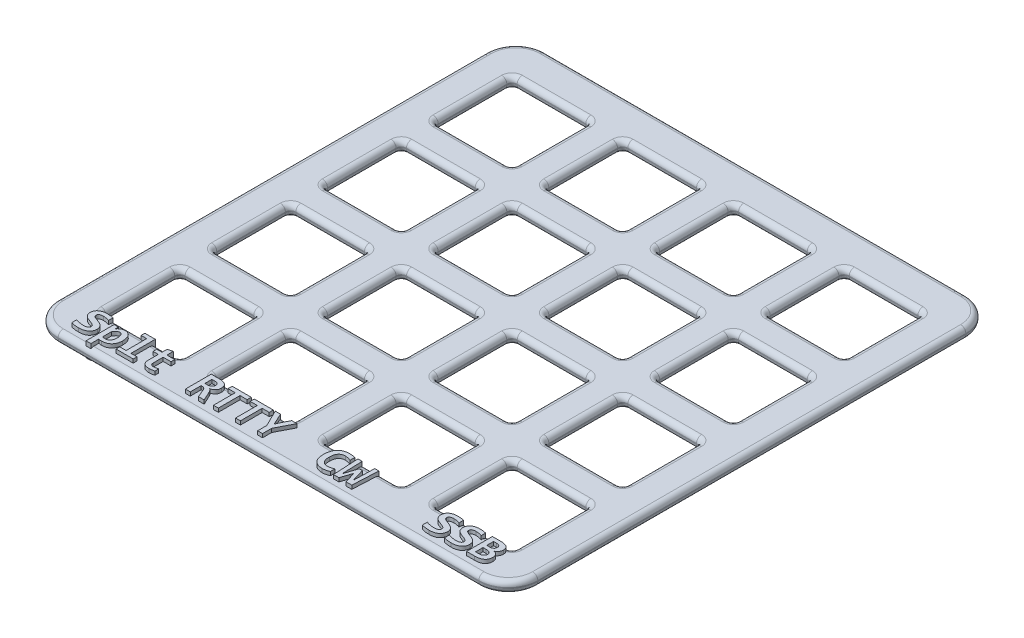
SolidWorks part; units mm, degrees
ref_plane "Front" through (0, 0, 0) normal (0, 0, 1) x (1, 0, 0)
ref_plane "Top" through (0, 0, 0) normal (0, 1, 0) x (1, 0, 0)
ref_plane "Right" through (0, 0, 0) normal (1, 0, 0) x (0, 0, -1)
sketch "Sketch1" plane through (0, 0, 0) normal (0, 1, 0) x (1, 0, 0)
  line L1 (-14.8807, -14.5355) -> (42.1193, -14.5355)
  line L2 (-18.8807, -18.5355) -> (-18.8807, -76.5355)
  line L3 (-14.8807, -80.5355) -> (42.1193, -80.5355)
  line L4 (46.1193, -18.5355) -> (46.1193, -76.5355)
  arc A0 (-14.8807, -14.5355) -> (-18.8807, -18.5355) centre (-14.8807, -18.5355) ccw
  arc A1 (46.1193, -18.5355) -> (42.1193, -14.5355) centre (42.1193, -18.5355) ccw
  arc A2 (42.1193, -80.5355) -> (46.1193, -76.5355) centre (42.1193, -76.5355) ccw
  arc A3 (-18.8807, -76.5355) -> (-14.8807, -80.5355) centre (-14.8807, -76.5355) ccw
  dimension "D1" = 65
  dimension "D2" = 66
extrude "main" add sketch "Sketch1" along normal blind 1.5
sketch "Sketch2" plane through (0, 1.5, 0) normal (0, 1, 0) x (1, 0, 0)
  line L0 (42.1193, -14.5355) -> (-14.8807, -14.5355) construction
  line L1 (-14.2307, -19.6855) -> (-3.5307, -19.6855)
  line L2 (-14.2307, -19.6855) -> (-14.2307, -30.3855)
  line L3 (-14.2307, -30.3855) -> (-3.5307, -30.3855)
  line L4 (-3.5307, -19.6855) -> (-3.5307, -30.3855)
  line L5 (-18.8807, -18.5355) -> (-18.8807, -76.5355) construction
  point P4 (-8.8807, -19.6855)
  dimension "D1" = 5.15
  dimension "D2" = 4.65
  dimension "D3" = 10.7
  dimension "D4" = 10.7
extrude "button hole 1" cut sketch "Sketch2" against normal through all
fillet "button fillet" radius 0.7 12 edges at (-8.8807, 0, 30.3855) (-8.8807, 1.5, 30.3855) (-8.8807, 0, 19.6855) (-8.8807, 1.5, 19.6855) (-3.5307, 0.75, 30.3855) (-3.5307, 0, 25.0355) (-3.5307, 0.75, 19.6855) (-3.5307, 1.5, 25.0355) (-14.2307, 0.75, 19.6855) (-14.2307, 0, 25.0355) (-14.2307, 0.75, 30.3855) (-14.2307, 1.5, 25.0355)
pattern_linear "buttons by 16" count 4 spacing 15 along (1, 0, 0) count 4 spacing 15 along (0, 0, 1) of "button fillet", "button hole 1"
fillet "outer edge fillet" radius 0.7 16 edges at (13.6193, 1.5, 14.5355) (13.6193, 0, 14.5355) (46.1193, 1.5, 47.5355) (46.1193, 0, 47.5355) (13.6193, 1.5, 80.5355) (13.6193, 0, 80.5355) (-18.8807, 1.5, 47.5355) (-18.8807, 0, 47.5355) (44.9477, 1.5, 15.7071) (44.9477, 1.5, 79.364) (-17.7092, 1.5, 79.364) (-17.7092, 1.5, 15.7071) (44.9477, 0, 15.7071) (44.9477, 0, 79.364) (-17.7092, 0, 79.364) (-17.7092, 0, 15.7071)
sketch "Lettering" plane through (0, 0, 0) normal (0, 1, 0) x (1, 0, 0)
  line L0 (45.4193, -34.1355) -> (-18.1807, -34.1355) construction
  line L1 (45.4783, -49.1355) -> (-16.5217, -49.1355) construction
  line L2 (45.4193, -76.5355) -> (45.4193, -18.5355) construction
  line L3 (-18.1807, -18.5355) -> (-18.1807, -76.5355) construction
  line L5 (45.4193, -64.1355) -> (-18.1807, -64.1355) construction
  line L6 (45.4193, -76.5355) -> (45.4193, -18.5355) construction
  line L7 (-18.1807, -18.5355) -> (-18.1807, -76.5355) construction
  line L8 (45.4193, -79.1355) -> (-18.1807, -79.1355) construction
  line L11 (-14.8807, -80.5355) -> (42.1193, -80.5355) construction
  text T0 "SSB" font "Consolas" height 3.5
  text T1 "CW" font "Consolas" height 3.5
  text T2 "RTTY" font "Consolas" height 3.5
  text T3 "Splt" font "Consolas" height 3.5
  dimension "D1" = 1.4
  dimension "D2" = 16.4
  dimension "D3" = 31.4
  dimension "D4" = 46.4
extrude "lettering boss" add sketch "Lettering" along normal offset from surface (2 mm away) 0.5 up to face at (13.6193, 1.5, 47.5355) offset beyond the face yes
